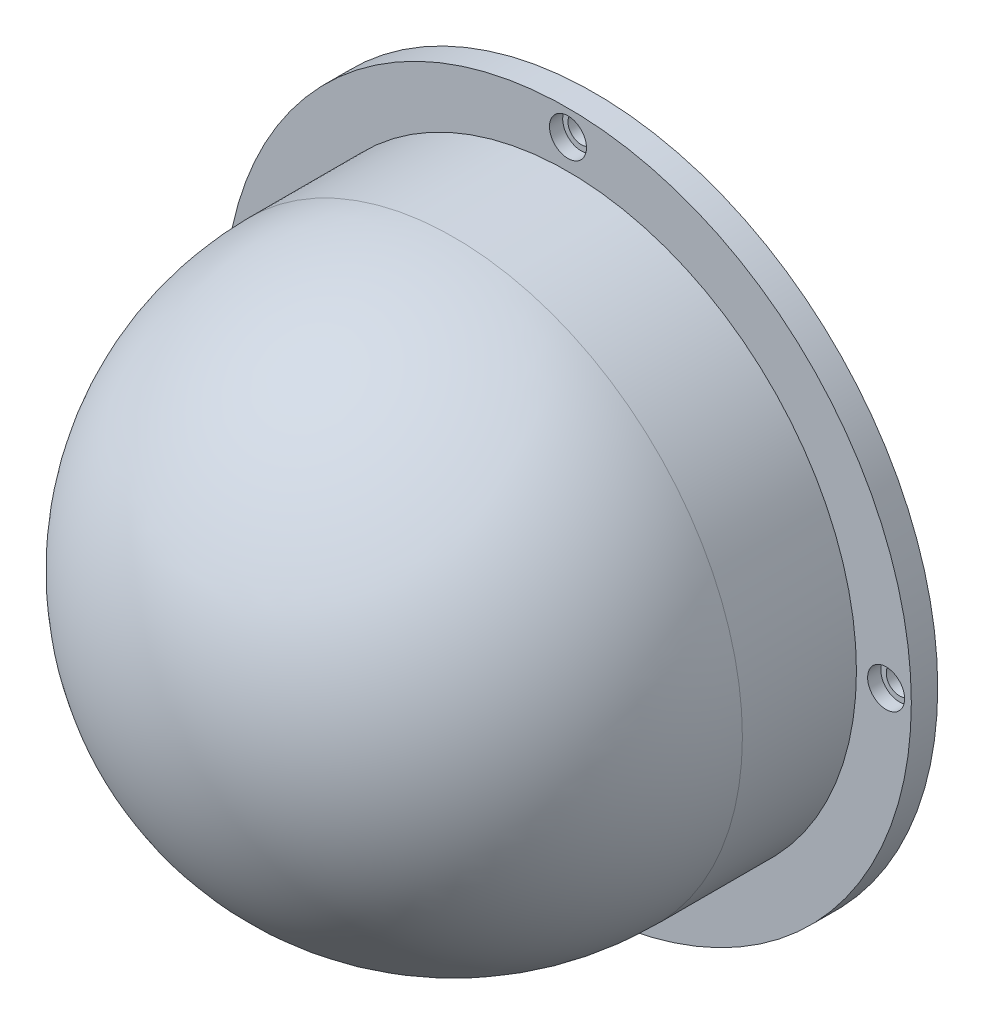
SolidWorks part; units mm, degrees
ref_plane "Front Plane" through (0, 0, 0) normal (1, 0, 0) x (0, 1, 0)
ref_plane "Top Plane" through (0, 0, 0) normal (0, 0, 1) x (0, 1, 0)
ref_plane "Right Plane" through (0, 0, 0) normal (0, 1, 0) x (-1, 0, 0)
sketch "Sketch2" plane through (0, 0, 0) normal (0, 0, 1) x (0, 1, 0)
  circle A0 centre (0, 0) radius 65
  dimension "D1" = 130
extrude "Boss-Extrude1" add sketch "Sketch2" along normal blind 5
sketch "Sketch3" plane through (0, 0, 5) normal (0, 0, 1) x (1, 0, 0)
  circle A0 centre (0, 0) radius 54.61
  dimension "D1" = 109.22
extrude "Boss-Extrude2" add sketch "Sketch3" along normal blind 76.2
fillet "Fillet8" radius 54.61 1 edges at (54.61, 0, 81.2)
shell "Shell1" thickness 5 removed face at (65, 0, 0)
sketch "Sketch7" plane through (0, 0, 5) normal (0, 0, 1) x (1, 0, 0)
  circle A0 centre (0, 60.2478) radius 2.5
  dimension "D1" = 5
extrude "Cut-Extrude2" cut sketch "Sketch7" against normal blind 5
sketch "Sketch8" plane through (0, 0, 5) normal (0, 0, 1) x (1, 0, 0)
  circle A0 centre (0, 60.2236) radius 3.5
  dimension "D1" = 7
extrude "Cut-Extrude3" cut sketch "Sketch8" against normal blind 2.5
pattern_circular "CirPattern1" count 4 over 360 about axis through (0, 0, 5) along (0, 0, -1) of "Cut-Extrude3", "Cut-Extrude2" reverse direction yes
